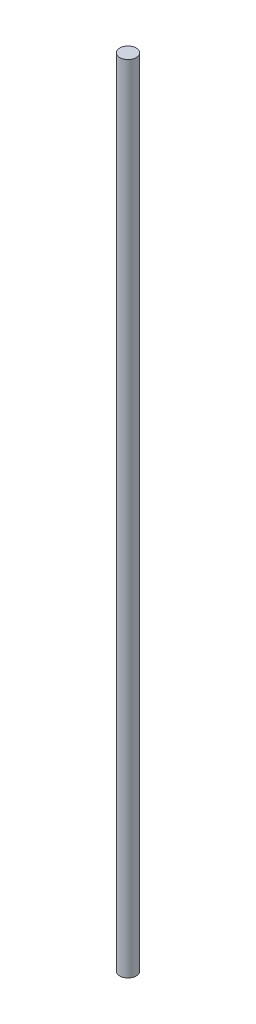
SolidWorks part; units mm, degrees
material "6061 Alloy"
ref_plane "Front Plane" through (0, 0, 0) normal (0, 0, 1) x (1, 0, 0)
ref_plane "Top Plane" through (0, 0, 0) normal (0, 1, 0) x (1, 0, 0)
ref_plane "Right Plane" through (0, 0, 0) normal (1, 0, 0) x (0, 0, -1)
sketch "Sketch1" plane through (0, 0, 0) normal (0, 1, 0) x (1, 0, 0)
  circle A0 centre (0, 0) radius 6.35
  dimension "D1" = 12.7
extrude "Boss-Extrude1" add sketch "Sketch1" along normal blind 609.6
